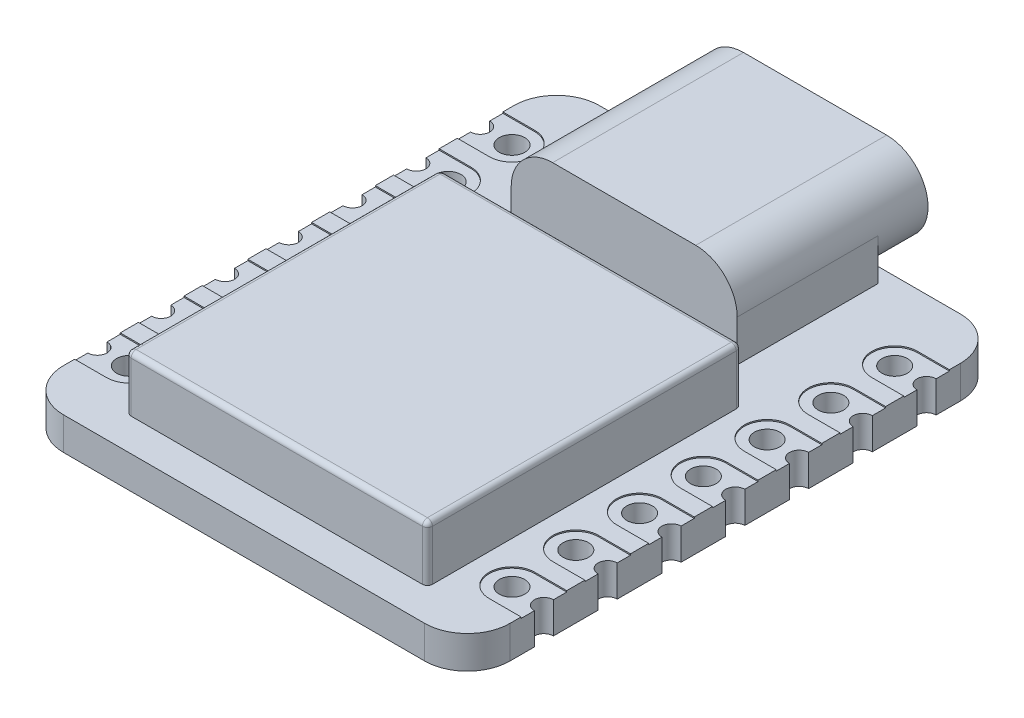
SolidWorks part; units mm, degrees
ref_plane "Front Plane" through (0, 0, 0) normal (0, 0, 1) x (1, 0, 0)
ref_plane "Top Plane" through (0, 0, 0) normal (0, 1, 0) x (1, 0, 0)
ref_plane "Right Plane" through (0, 0, 0) normal (1, 0, 0) x (0, 0, -1)
sketch "Sketch1" plane through (0, 0, 0) normal (0, 1, 0) x (1, 0, 0)
  line L1 (8.89, -10.668) -> (-8.89, -10.668)
  line L2 (8.89, -10.668) -> (8.89, 10.668)
  line L3 (8.89, 10.668) -> (-8.89, 10.668)
  line L4 (-8.89, -10.668) -> (-8.89, 10.668)
  line L5 (8.89, -10.668) -> (-8.89, 10.668) construction
  line L6 (8.89, 10.668) -> (-8.89, -10.668) construction
  point P0 (0, 0)
  dimension "D1" = 17.78
  dimension "D2" = 21.336
extrude "Boss-Extrude1" add sketch "Sketch1" along normal blind 1.3
sketch "Sketch2" plane through (0, 1.3, 0) normal (0, 1, 0) x (1, 0, 0)
  line L0 (-8.89, -10.668) -> (8.89, -10.668) construction
  line L1 (-6, 3.132) -> (6, 3.132)
  line L2 (-6, 3.132) -> (-6, -9.368)
  line L3 (-6, -9.368) -> (6, -9.368)
  line L4 (6, 3.132) -> (6, -9.368)
  line L5 (-6, 3.132) -> (6, -9.368) construction
  line L6 (-6, -9.368) -> (6, 3.132) construction
  point P0 (0, -3.118)
  dimension "D1" = 12
  dimension "D2" = 12.5
  dimension "D3" = 1.3
extrude "Boss-Extrude2" add sketch "Sketch2" along normal blind 2.2
sketch "Sketch4" plane through (0, 1.3, 0) normal (0, 1, 0) x (1, 0, 0)
  line L0 (0, 4.468) -> (0, 0) construction
  line L1 (4.5, 4.468) -> (-4.5, 4.468)
  line L2 (4.5, 4.468) -> (4.5, 12.068)
  line L3 (4.5, 12.068) -> (-4.5, 12.068)
  line L4 (-4.5, 4.468) -> (-4.5, 12.068)
  line L5 (8.89, 10.668) -> (-8.89, 10.668) construction
  dimension "D1" = 9
  dimension "D2" = 7.6
  dimension "D3" = 1.4
extrude "Boss-Extrude3" add sketch "Sketch4" along normal blind 3.3
sketch "Sketch5" plane through (0, 0, -12.068) normal (0, 0, -1) x (-1, 0, 0)
  line L0 (-2.85, 4.6) -> (2.85, 4.6)
  line L1 (-4.5, 4.6) -> (4.5, 4.6) construction
  line L2 (2.85, 1.3) -> (-2.85, 1.3)
  line L3 (-4.5, 1.3) -> (4.5, 1.3) construction
  line L4 (4.5, 4.6) -> (4.5, 1.3) construction
  line L5 (-4.5, 4.6) -> (-4.5, 1.3) construction
  line L6 (-4.5, 2.95) -> (4.5, 2.95)
  arc A0 (2.85, 4.6) -> (2.85, 1.3) centre (2.85, 2.95) cw
  arc A1 (-2.85, 1.3) -> (-2.85, 4.6) centre (-2.85, 2.95) cw
  line M5 (-4.5, 1.3) -> (4.5, 1.3)
  line M6 (4.5, 1.3) -> (4.5, 4.6)
  line M7 (4.5, 4.6) -> (-4.5, 4.6)
  line M8 (-4.5, 4.6) -> (-4.5, 1.3)
extrude "Cut-Extrude1" cut sketch "Sketch5" against normal blind 2 contours A1 M5 M8 | A0 M6 M5 region at (4.1314, 1.6686, -12.068) region at (-4.1314, 1.6686, -12.068)
extrude "Cut-Extrude2" cut sketch "Sketch5<3>" against normal up to surface (7.6 mm away) contours A0 M7 M6 | A1 M8 M7 region at (4.1314, 4.2314, -12.068) region at (-4.1314, 4.2314, -12.068) up to face at (0, 2.95, -4.468)
sketch "Sketch5<3>" plane through (0, 0, -12.068) normal (0, 0, -1) x (-1, 0, 0) same geometry as "Sketch5"
fillet "Fillet1" radius 0.2 8 edges at (6, 3.5, 3.118) (0, 3.5, -3.132) (0, 3.5, 9.368) (6, 2.4, 9.368) (-6, 2.4, 9.368) (-6, 2.4, -3.132) (6, 2.4, -3.132) (-6, 3.5, 3.118)
fillet "Fillet2" radius 1.7 4 edges at (8.89, 0.65, 10.668) (8.89, 0.65, -10.668) (-8.89, 0.65, -10.668) (-8.89, 0.65, 10.668)
sketch "Sketch6" plane through (0, 1.3, 0) normal (0, 1, 0) x (1, 0, 0)
  line L0 (-8.89, 8.968) -> (-8.89, -8.968) construction
  circle A0 centre (-7.62, 7.62) radius 0.508
  circle A1 centre (-8.89, 7.62) radius 0.381
  dimension "D2" = 1.016
  dimension "D3" = 0.762
  dimension "D1" = 7.62
  dimension "D4" = 7.62
extrude "Cut-Extrude3" cut sketch "Sketch6" against normal through all
sketch "Sketch7" plane through (0, 1.3, 0) normal (0, 1, 0) x (1, 0, 0)
  line L0 (-8.89, 8.528) -> (-7.62, 8.528)
  line L1 (-8.89, 8.968) -> (-8.89, 8.001) construction
  line L2 (-7.62, 6.712) -> (-8.89, 6.712)
  line L3 (-8.89, 6.712) -> (-8.89, 8.528)
  arc A0 (-7.62, 8.528) -> (-7.62, 6.712) centre (-7.62, 7.62) cw
  circle A1 centre (-7.62, 7.62) radius 0.508 construction
  dimension "D1" = 0.4
extrude "Cut-Extrude4" cut sketch "Sketch7" against normal blind 0.05
pattern_linear "LPattern1" count 7 spacing 2.54 along (0, 0, 1) of "Cut-Extrude3", "Cut-Extrude4"
mirror "Mirror1" about plane through (0, 0, 0) normal (1, 0, 0) of "LPattern1"
sketch "Sketch8" plane through (0, 0, -12.068) normal (0, 0, -1) x (-1, 0, 0)
  line L4 (2.85, 4.4) -> (-2.85, 4.4)
  line L5 (-2.85, 1.5) -> (2.85, 1.5)
  line L6 (2.85, 4.4) -> (-2.85, 4.4)
  line L7 (-2.85, 1.5) -> (2.85, 1.5)
  arc A4 (2.85, 1.5) -> (2.85, 4.4) centre (2.85, 2.95) ccw
  arc A5 (-2.85, 4.4) -> (-2.85, 1.5) centre (-2.85, 2.95) ccw
  arc A6 (2.85, 1.5) -> (2.85, 4.4) centre (2.85, 2.95) ccw
  arc A7 (-2.85, 4.4) -> (-2.85, 1.5) centre (-2.85, 2.95) ccw
  dimension "D1" = 0.2
extrude "Cut-Extrude5" cut sketch "Sketch8" against normal blind 5
